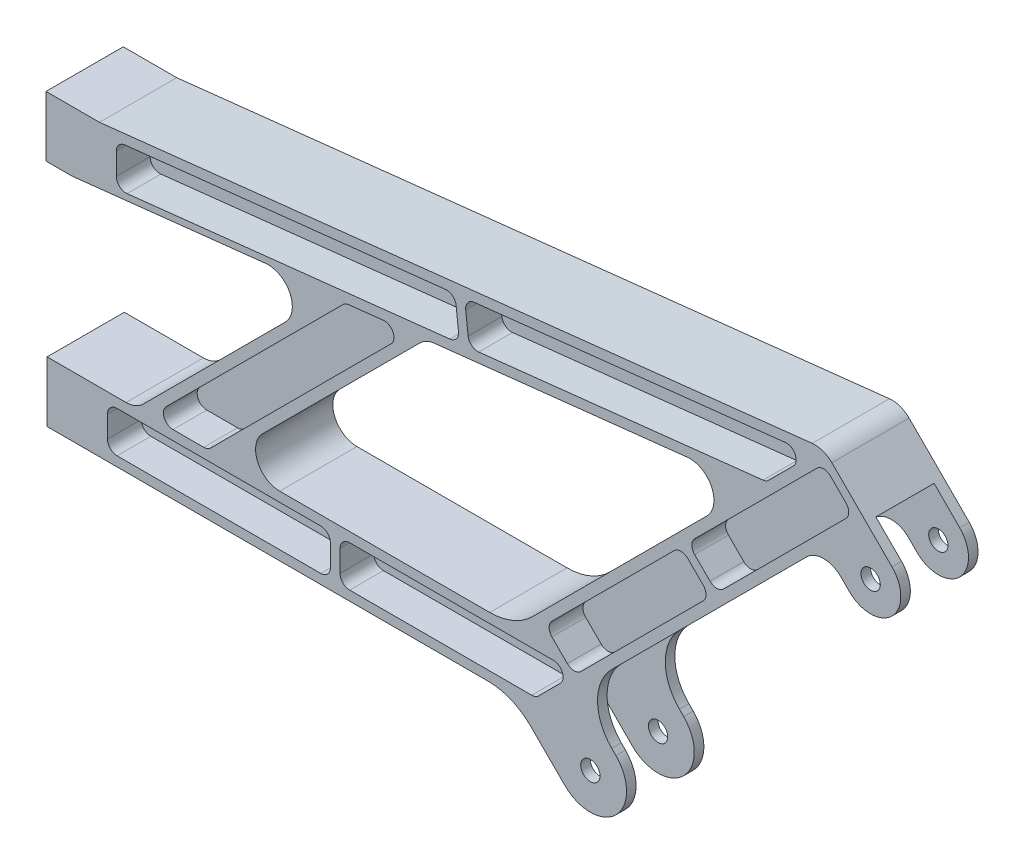
SolidWorks part; units mm, degrees
material "6061-T6 (SS)"
ref_plane "Front Plane" through (0, 0, 0) normal (0, 0, 1) x (1, 0, 0)
ref_plane "Top Plane" through (0, 0, 0) normal (0, 1, 0) x (1, 0, 0)
ref_plane "Right Plane" through (0, 0, 0) normal (1, 0, 0) x (0, 0, -1)
sketch "Sketch1" plane through (0, 0, 0) normal (0, 0, 1) x (1, 0, 0)
  line L1 (-157.7639, -90.8401) -> (-244.7728, -90.8401)
  line L2 (-67.8181, -11.2496) -> (-140.0863, -83.5177)
  line L3 (-16.0497, 33.7315) -> (8.8396, 8.8381)
  line L4 (-12.3744, -5.3033) -> (-8.8388, -8.8388)
  line L5 (-26.5165, -5.3033) -> (-107.2487, -86.0355)
  line L6 (-140.8326, -123.1624) -> (-126.6942, -137.3008)
  line L7 (-158.5102, -115.8401) -> (-341.1373, -115.8401)
  line L8 (-341.1373, -115.8401) -> (-341.1373, -90.8401)
  line L9 (-308.4124, -90.8401) -> (-341.1373, -90.8401)
  line L11 (-341.5776, -20.8403) -> (-331.2717, -20.8403)
  line L12 (-341.5776, -20.8403) -> (-341.5776, 4.1597)
  line L13 (-341.5776, 4.1597) -> (-319.4176, 4.1597)
  line L14 (-107.2487, -114.3198) -> (-105.481, -116.0876)
  line L15 (-319.4176, 4.1597) -> (-24.2138, 36.6012)
  line L17 (-301.3413, -87.9111) -> (-242.4814, -29.0512)
  line L18 (-75.9816, 5.7616) -> (-180.7131, -5.7479)
  line L19 (-251.8438, -73.769) -> (-186.6918, -8.6169)
  line L20 (-250.6448, -12.04) -> (-330.1793, -20.7804)
  arc A4 (8.8388, -8.8388) -> (8.8396, 8.8381) centre (0, 0) ccw
  arc A5 (-8.8388, -8.8388) -> (8.8388, -8.8388) centre (0, 0) ccw
  arc A6 (-12.3744, -5.3033) -> (-26.5165, -5.3033) centre (-19.4454, -12.3744) ccw
  arc A7 (-107.2487, -86.0355) -> (-107.2487, -114.3198) centre (-93.1066, -100.1777) ccw
  arc A8 (-105.481, -137.3008) -> (-105.481, -116.0876) centre (-116.0876, -126.6942) ccw
  arc A9 (-126.6942, -137.3008) -> (-105.481, -137.3008) centre (-116.0876, -126.6942) ccw
  circle A12 centre (-116.0876, -126.6942) radius 4
  circle A13 centre (0, 0) radius 4
  arc A15 (-158.5102, -115.8401) -> (-140.8326, -123.1624) centre (-158.5102, -140.8401) cw
  arc A16 (-157.7639, -90.8401) -> (-140.0863, -83.5177) centre (-157.7639, -65.8401) ccw
  arc A20 (-67.8181, -11.2496) -> (-75.9816, 5.7616) centre (-74.8892, -4.1785) ccw
  arc A21 (-16.0497, 33.7315) -> (-24.2138, 36.6012) centre (-23.1214, 26.661) ccw
  arc A22 (-186.6918, -8.6169) -> (-180.7131, -5.7479) centre (-179.6207, -15.688) cw
  arc A23 (-244.7728, -90.8401) -> (-251.8438, -73.769) centre (-244.7728, -80.8401) cw
  arc A24 (-330.1793, -20.7804) -> (-331.2717, -20.8403) centre (-331.2717, -10.8403) cw
  arc A25 (-308.4124, -90.8401) -> (-301.3413, -87.9111) centre (-308.4124, -80.8401) ccw
  arc A26 (-250.6448, -12.04) -> (-242.4814, -29.0512) centre (-249.5525, -21.9802) cw
  point P50 (-309.0268, -89.6685)
  dimension "D2" = 25
  dimension "D3" = 25
  dimension "D7" = 10
  dimension "D6" = 25
  dimension "D1" = 25
  dimension "D4" = 25
  dimension "D5" = 25
  dimension "D8" = 119.9998
extrude "Boss-Extrude1" add sketch "Sketch1" along normal blind 32
sketch "Sketch2" plane through (0, 0, 32) normal (0, 0, 1) x (1, 0, 0)
  line L0 (-107.2487, -86.0355) -> (-26.5165, -5.3033) construction
  line L1 (-137.5386, -110.6685) -> (-128.5386, -101.6685)
  line L2 (-131.367, -94.8401) -> (-215.77, -94.8401)
  line L3 (-67.8181, -11.2496) -> (-140.0863, -83.5177) construction
  line L4 (-107.2487, -86.0355) -> (-26.5165, -5.3033)
  line L5 (-67.8181, -11.2496) -> (-140.0863, -83.5177)
  line L6 (-22.272, 28.6397) -> (-72.893, -21.9813)
  line L7 (-119.9767, -93.1066) -> (-69.3575, -42.4874)
  line L8 (-131.9975, -86.7426) -> (-125.6335, -93.1066)
  line L9 (-10.2515, 22.275) -> (-16.6149, 28.6394)
  line L10 (-64.9897, -14.078) -> (-137.2579, -86.3462) construction
  line L11 (-110.0772, -83.2071) -> (-29.3449, -2.4749) construction
  line L12 (-341.1373, -115.8401) -> (-158.5102, -115.8401) construction
  line L13 (-341.1373, -115.8401) -> (-158.5102, -115.8401)
  line L14 (-312.1373, -111.8401) -> (-227.77, -111.8401)
  line L15 (-341.1373, -111.8401) -> (-158.5102, -111.8401) construction
  line L16 (-341.1373, -90.8401) -> (-341.1373, -115.8401) construction
  line L17 (-316.1373, -98.8401) -> (-316.1373, -107.8401)
  line L18 (-157.7639, -90.8401) -> (-244.7728, -90.8401) construction
  line L19 (8.8396, 8.8381) -> (-16.0497, 33.7315) construction
  line L20 (-140.8326, -123.1624) -> (-126.6942, -137.3008) construction
  line L21 (-65.1149, -38.2448) -> (-77.1357, -26.224) construction
  line L22 (-72.893, -27.6382) -> (-66.5291, -34.0022)
  line L23 (-75.7215, -30.4666) -> (-69.3575, -36.8306)
  line L24 (-81.3783, -30.4666) -> (-131.9975, -81.0858)
  line L25 (-60.8722, -34.0022) -> (-10.2517, 16.6183)
  line L26 (-221.77, -94.8401) -> (-221.77, -111.8401) construction
  line L27 (-219.77, -98.8401) -> (-219.77, -107.8401)
  line L28 (-223.77, -98.8401) -> (-223.77, -107.8401)
  line L29 (-215.77, -111.8401) -> (-140.367, -111.8401)
  line L30 (-227.77, -94.8401) -> (-312.1373, -94.8401)
  line L38 (-308.8907, 1.2925) -> (-176.1091, 15.8845)
  line L39 (-24.2138, 36.6012) -> (-319.4176, 4.1597) construction
  line L40 (-308.0168, -15.7138) -> (-174.2521, -1.0137)
  line L41 (-75.9816, 5.7616) -> (-180.7131, -5.7479) construction
  line L42 (-312.4538, -2.6836) -> (-312.4538, -11.7378)
  line L43 (-32.0118, 24.5568) -> (-42.1838, 14.3847)
  line L44 (-170.145, 16.5399) -> (-168.288, -0.3583) construction
  line L45 (-171.6961, 12.3454) -> (-170.713, 3.3993)
  line L46 (-167.7201, 12.7824) -> (-166.7369, 3.8362)
  line L47 (-164.181, 17.1954) -> (-35.2771, 31.3613)
  line L48 (-162.3239, 0.2971) -> (-44.5753, 13.2371)
  line L49 (-218.5658, -10.7925) -> (-291.7849, -84.0116)
  line L50 (-242.4814, -29.0512) -> (-301.3413, -87.9111) construction
  line L51 (-198.6096, -14.8779) -> (-273.4002, -89.6685)
  line L52 (-186.6918, -8.6169) -> (-251.8438, -73.769) construction
  line L53 (-216.1743, -9.6449) -> (-201.875, -8.0734)
  line L54 (-288.9565, -90.8401) -> (-276.2286, -90.8401)
  line L55 (-341.5776, 4.1597) -> (-341.5776, -20.8403) construction
  arc A0 (-22.272, 28.6397) -> (-16.6149, 28.6394) centre (-19.4436, 25.8113) cw
  arc A1 (-10.2517, 16.6183) -> (-10.2515, 22.275) centre (-13.0801, 19.4468) ccw
  arc A2 (-119.9767, -93.1066) -> (-125.6335, -93.1066) centre (-122.8051, -90.2782) cw
  arc A3 (-131.9975, -81.0858) -> (-131.9975, -86.7426) centre (-129.169, -83.9142) ccw
  arc A4 (-312.1373, -111.8401) -> (-316.1373, -107.8401) centre (-312.1373, -107.8401) cw
  arc A5 (-312.1373, -94.8401) -> (-316.1373, -98.8401) centre (-312.1373, -98.8401) ccw
  arc A6 (-140.367, -111.8401) -> (-137.5386, -110.6685) centre (-140.367, -107.8401) ccw
  arc A7 (-128.5386, -101.6685) -> (-131.367, -94.8401) centre (-131.367, -98.8401) ccw
  arc A8 (-75.7215, -30.4666) -> (-81.3783, -30.4666) centre (-78.5499, -33.295) ccw
  arc A9 (-69.3575, -36.8306) -> (-69.3575, -42.4874) centre (-72.1859, -39.659) cw
  arc A10 (-66.5291, -34.0022) -> (-60.8722, -34.0022) centre (-63.7006, -31.1737) ccw
  arc A11 (-72.893, -27.6382) -> (-72.893, -21.9813) centre (-70.0646, -24.8098) cw
  arc A12 (-223.77, -107.8401) -> (-227.77, -111.8401) centre (-227.77, -107.8401) cw
  arc A13 (-219.77, -107.8401) -> (-215.77, -111.8401) centre (-215.77, -107.8401) ccw
  arc A14 (-219.77, -98.8401) -> (-215.77, -94.8401) centre (-215.77, -98.8401) cw
  arc A15 (-223.77, -98.8401) -> (-227.77, -94.8401) centre (-227.77, -98.8401) ccw
  arc A20 (-44.5753, 13.2371) -> (-42.1838, 14.3847) centre (-45.0122, 17.2132) ccw
  arc A21 (-35.2771, 31.3613) -> (-32.0118, 24.5568) centre (-34.8402, 27.3852) cw
  arc A22 (-166.7369, 3.8362) -> (-162.3239, 0.2971) centre (-162.7609, 4.2732) ccw
  arc A23 (-167.7201, 12.7824) -> (-164.181, 17.1954) centre (-163.744, 13.2193) cw
  arc A24 (-170.713, 3.3993) -> (-174.2521, -1.0137) centre (-174.6891, 2.9623) cw
  arc A25 (-171.6961, 12.3454) -> (-176.1091, 15.8845) centre (-175.6722, 11.9085) ccw
  arc A26 (-308.0168, -15.7138) -> (-312.4538, -11.7378) centre (-308.4538, -11.7378) cw
  arc A27 (-308.8907, 1.2925) -> (-312.4538, -2.6836) centre (-308.4538, -2.6836) ccw
  arc A28 (-198.6096, -14.8779) -> (-201.875, -8.0734) centre (-201.438, -12.0495) ccw
  arc A29 (-218.5658, -10.7925) -> (-216.1743, -9.6449) centre (-215.7374, -13.6209) cw
  arc A30 (-273.4002, -89.6685) -> (-276.2286, -90.8401) centre (-276.2286, -86.8401) cw
  arc A31 (-288.9565, -90.8401) -> (-291.7849, -84.0116) centre (-288.9565, -86.8401) cw
  point P34 (-316.1373, -111.8401)
  point P53 (-78.5499, -27.6382)
  point P58 (-63.7006, -36.8306)
  point P69 (-223.77, -111.8401)
  point P72 (-219.77, -111.8401)
  point P75 (-219.77, -94.8401)
  point P78 (-223.77, -94.8401)
  point P117 (-166.3, -0.1398)
  point P120 (-168.157, 16.7584)
  point P123 (-170.276, -0.5768)
  point P126 (-172.1331, 16.3215)
  dimension "D2" = 4
  dimension "D6" = 4
  dimension "D11" = 4
  dimension "D13" = 4
  dimension "D16" = 4
  dimension "D22" = 4
  dimension "D19" = 4
  dimension "D4" = 25
  dimension "D5" = 4
  dimension "D7" = 4
  dimension "D8" = 4
  dimension "D9" = 32
  dimension "D10" = 2
  dimension "D12" = 2
  dimension "D14" = 4
  dimension "D15" = 4
  dimension "D17" = 4
  dimension "D18" = 4
  dimension "D20" = 4
  dimension "D21" = 2
  dimension "D23" = 4
  dimension "D1" = 4
  dimension "D3" = 4
extrude "Cut-Extrude1" cut sketch "Sketch2" against normal blind 14 contours L38 A27 L42 A26 L40 A24 L45 A25 | A23 L46 A22 L48 A20 L43 A21 L47 | A31 L54 A30 L51 A28 L53 A29 L49 | A11 L22 A10 L25 A1 L9 A0 L6 | A9 L23 A8 L24 A3 L8 A2 L7 | A14 L27 A13 L29 A6 L1 A7 L2 | L28 A15 L30 A5 L17 A4 L14 A12 region at (-175.3079, -103.1533, 32) region at (-41.5723, -2.6814, 32) region at (-100.6775, -61.7866, 32) region at (-269.9537, -103.3401, 32) region at (-241.8227, 0.0982, 32) region at (-100.9045, 15.7508, 32) region at (-245.4094, -49.7028, 32)
ref_plane "Plane1" through (0, 0, 16) normal (0, 0, 1) x (1, 0, 0)
mirror "Mirror1" about plane through (0, 0, 16) normal (0, 0, 1) of "Cut-Extrude1"
sketch "Sketch3" plane through (0, 0, 16) normal (0, 0, 1) x (1, 0, 0)
  line L0 (-158.5102, -115.8401) -> (-141.1954, -115.8401)
  line L1 (-98.969, -77.7558) -> (-134.1243, -112.9111)
  line L2 (-107.2487, -86.0355) -> (-26.5165, -5.3033) construction
  line L3 (-158.5102, -115.8401) -> (-116.5971, -149.2186)
  line L4 (-116.5971, -149.2186) -> (-66.3597, -110.0186)
  line L5 (-66.3597, -110.0186) -> (-98.969, -77.7558)
  line L6 (-29.0156, -7.8024) -> (7.8698, 29.083)
  line L7 (7.8698, 29.083) -> (26.3533, -15.3879)
  line L8 (26.3533, -15.3879) -> (-12.041, -17.819)
  line L9 (-12.041, -17.819) -> (-29.0156, -7.8024)
  arc A0 (-134.1243, -112.9111) -> (-141.1954, -115.8401) centre (-141.1954, -105.8401) cw
  dimension "D1" = 10
extrude "Cut-Extrude2" cut sketch "Sketch3" against normal blind 12.0515 and the other way blind 12.0515
sketch "Sketch5" plane through (0, 0, 16) normal (0, 0, 1) x (1, 0, 0)
  line L0 (0, -24.7236) -> (0, -90.9031)
